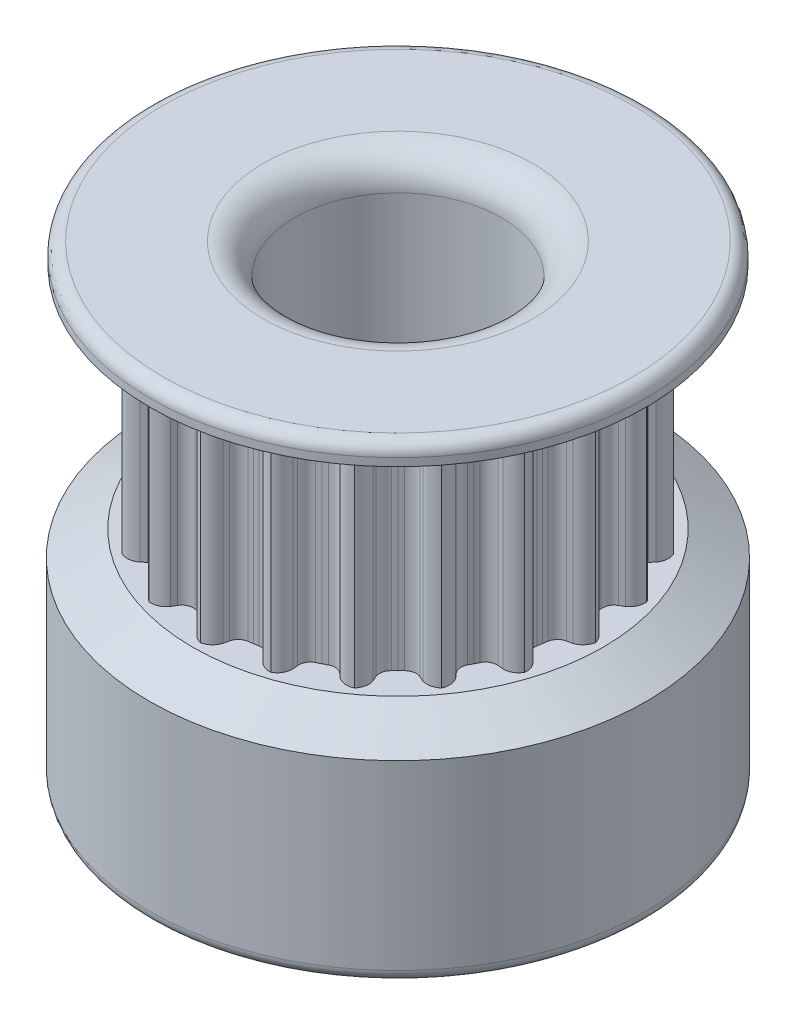
SolidWorks part; units mm, degrees
ref_plane "Plan de face" through (0, 0, 0) normal (0, 0, 1) x (1, 0, 0)
ref_plane "Plan de dessus" through (0, 0, 0) normal (0, 1, 0) x (1, 0, 0)
ref_plane "Plan de droite" through (0, 0, 0) normal (1, 0, 0) x (0, 0, -1)
sketch "Esquisse1" plane through (0, 0, 0) normal (0, 1, 0) x (1, 0, 0)
  circle A0 centre (0, 0) radius 7.935
  dimension "D1" = 15.87
extrude "Boss.-Extru.1" add sketch "Esquisse1" along normal blind 7
sketch "Esquisse2" plane through (0, 7, 0) normal (0, 1, 0) x (1, 0, 0)
  line L0 (0, 0) -> (0, 10.3573) construction
  line L1 (0, 0) -> (-1.2413, 7.8373) construction
  line L2 (0, 0) -> (1.2413, 7.8373) construction
  line L3 (-0.8681, 5.4812) -> (-0.7197, 5.5031)
  line L4 (-0.4122, 5.7909) -> (-0.3761, 5.9574)
  line L5 (0.4122, 5.7909) -> (0.3761, 5.9574)
  line L6 (0.8681, 5.4812) -> (0.7197, 5.5031)
  line L7 (2.5194, 4.9447) -> (2.3851, 5.0114)
  line L8 (1.3974, 5.6348) -> (1.4832, 5.7821)
  line L9 (0.8681, 5.4812) -> (1.016, 5.4562)
  line L10 (2.1815, 5.3801) -> (2.1987, 5.5496)
  line L11 (3.9241, 3.9241) -> (3.8169, 4.0291)
  line L12 (3.0703, 4.9272) -> (3.1974, 5.0407)
  line L13 (2.5194, 4.9447) -> (2.6524, 4.8752)
  line L14 (3.7373, 4.4426) -> (3.806, 4.5985)
  line L15 (4.9447, 2.5194) -> (4.8752, 2.6524)
  line L16 (4.4426, 3.7373) -> (4.5985, 3.806)
  line L17 (3.9241, 3.9241) -> (4.0291, 3.8169)
  line L18 (4.9272, 3.0703) -> (5.0407, 3.1974)
  line L19 (5.4812, 0.8681) -> (5.4562, 1.016)
  line L20 (5.3801, 2.1815) -> (5.5496, 2.1987)
  line L21 (4.9447, 2.5194) -> (5.0114, 2.3851)
  line L22 (5.6348, 1.3974) -> (5.7821, 1.4832)
  line L23 (5.4812, -0.8681) -> (5.5031, -0.7197)
  line L24 (5.7909, 0.4122) -> (5.9574, 0.3761)
  line L25 (5.4812, 0.8681) -> (5.5031, 0.7197)
  line L26 (5.7909, -0.4122) -> (5.9574, -0.3761)
  line L27 (4.9447, -2.5194) -> (5.0114, -2.3851)
  line L28 (5.6348, -1.3974) -> (5.7821, -1.4832)
  line L29 (5.4812, -0.8681) -> (5.4562, -1.016)
  line L30 (5.3801, -2.1815) -> (5.5496, -2.1987)
  line L31 (3.9241, -3.9241) -> (4.0291, -3.8169)
  line L32 (4.9272, -3.0703) -> (5.0407, -3.1974)
  line L33 (4.9447, -2.5194) -> (4.8752, -2.6524)
  line L34 (4.4426, -3.7373) -> (4.5985, -3.806)
  line L35 (2.5194, -4.9447) -> (2.6524, -4.8752)
  line L36 (3.7373, -4.4426) -> (3.806, -4.5985)
  line L37 (3.9241, -3.9241) -> (3.8169, -4.0291)
  line L38 (3.0703, -4.9272) -> (3.1974, -5.0407)
  line L39 (0.8681, -5.4812) -> (1.016, -5.4562)
  line L40 (2.1815, -5.3801) -> (2.1987, -5.5496)
  line L41 (2.5194, -4.9447) -> (2.3851, -5.0114)
  line L42 (1.3974, -5.6348) -> (1.4832, -5.7821)
  line L43 (-0.8681, -5.4812) -> (-0.7197, -5.5031)
  line L44 (0.4122, -5.7909) -> (0.3761, -5.9574)
  line L45 (0.8681, -5.4812) -> (0.7197, -5.5031)
  line L46 (-0.4122, -5.7909) -> (-0.3761, -5.9574)
  line L47 (-2.5194, -4.9447) -> (-2.3851, -5.0114)
  line L48 (-1.3974, -5.6348) -> (-1.4832, -5.7821)
  line L49 (-0.8681, -5.4812) -> (-1.016, -5.4562)
  line L50 (-2.1815, -5.3801) -> (-2.1987, -5.5496)
  line L51 (-3.9241, -3.9241) -> (-3.8169, -4.0291)
  line L52 (-3.0703, -4.9272) -> (-3.1974, -5.0407)
  line L53 (-2.5194, -4.9447) -> (-2.6524, -4.8752)
  line L54 (-3.7373, -4.4426) -> (-3.806, -4.5985)
  line L55 (-4.9447, -2.5194) -> (-4.8752, -2.6524)
  line L56 (-4.4426, -3.7373) -> (-4.5985, -3.806)
  line L57 (-3.9241, -3.9241) -> (-4.0291, -3.8169)
  line L58 (-4.9272, -3.0703) -> (-5.0407, -3.1974)
  line L59 (-5.4812, -0.8681) -> (-5.4562, -1.016)
  line L60 (-5.3801, -2.1815) -> (-5.5496, -2.1987)
  line L61 (-4.9447, -2.5194) -> (-5.0114, -2.3851)
  line L62 (-5.6348, -1.3974) -> (-5.7821, -1.4832)
  line L63 (-5.4812, 0.8681) -> (-5.5031, 0.7197)
  line L64 (-5.7909, -0.4122) -> (-5.9574, -0.3761)
  line L65 (-5.4812, -0.8681) -> (-5.5031, -0.7197)
  line L66 (-5.7909, 0.4122) -> (-5.9574, 0.3761)
  line L67 (-4.9447, 2.5194) -> (-5.0114, 2.3851)
  line L68 (-5.6348, 1.3974) -> (-5.7821, 1.4832)
  line L69 (-5.4812, 0.8681) -> (-5.4562, 1.016)
  line L70 (-5.3801, 2.1815) -> (-5.5496, 2.1987)
  line L71 (-3.9241, 3.9241) -> (-4.0291, 3.8169)
  line L72 (-4.9272, 3.0703) -> (-5.0407, 3.1974)
  line L73 (-4.9447, 2.5194) -> (-4.8752, 2.6524)
  line L74 (-4.4426, 3.7373) -> (-4.5985, 3.806)
  line L75 (-2.5194, 4.9447) -> (-2.6524, 4.8752)
  line L76 (-3.7373, 4.4426) -> (-3.806, 4.5985)
  line L77 (-3.9241, 3.9241) -> (-3.8169, 4.0291)
  line L78 (-3.0703, 4.9272) -> (-3.1974, 5.0407)
  line L79 (-0.8681, 5.4812) -> (-1.016, 5.4562)
  line L80 (-2.1815, 5.3801) -> (-2.1987, 5.5496)
  line L81 (-2.5194, 4.9447) -> (-2.3851, 5.0114)
  line L82 (-1.3974, 5.6348) -> (-1.4832, 5.7821)
  circle A0 centre (0, 0) radius 6.3 construction
  circle A1 centre (0, 0) radius 7.935 construction
  circle A2 centre (0, 0) radius 5.55 construction
  arc A3 (-0.7197, 5.5031) -> (-0.4122, 5.7909) centre (-0.7738, 5.8692) ccw
  arc A4 (-0.3761, 5.9574) -> (0, 6.3) centre (0.1018, 5.8105) cw
  arc A5 (0.3761, 5.9574) -> (0, 6.3) centre (-0.1018, 5.8105) ccw
  arc A6 (0.7197, 5.5031) -> (0.4122, 5.7909) centre (0.7738, 5.8692) cw
  arc A7 (2.3851, 5.0114) -> (2.1815, 5.3801) centre (2.5496, 5.3428) cw
  arc A8 (2.1987, 5.5496) -> (1.9468, 5.9917) centre (1.6987, 5.5575) ccw
  arc A9 (1.4832, 5.7821) -> (1.9468, 5.9917) centre (1.8923, 5.4946) cw
  arc A10 (1.016, 5.4562) -> (1.3974, 5.6348) centre (1.0777, 5.821) ccw
  arc A11 (3.8169, 4.0291) -> (3.7373, 4.4426) centre (4.0758, 4.2934) cw
  arc A12 (3.806, 4.5985) -> (3.703, 5.0968) centre (3.333, 4.7606) ccw
  arc A13 (3.1974, 5.0407) -> (3.703, 5.0968) centre (3.4976, 4.6409) cw
  arc A14 (2.6524, 4.8752) -> (3.0703, 4.9272) centre (2.8238, 5.2031) ccw
  arc A15 (4.8752, 2.6524) -> (4.9272, 3.0703) centre (5.2031, 2.8238) cw
  arc A16 (5.0407, 3.1974) -> (5.0968, 3.703) centre (4.6409, 3.4976) ccw
  arc A17 (4.5985, 3.806) -> (5.0968, 3.703) centre (4.7606, 3.333) cw
  arc A18 (4.0291, 3.8169) -> (4.4426, 3.7373) centre (4.2934, 4.0758) ccw
  arc A19 (5.4562, 1.016) -> (5.6348, 1.3974) centre (5.821, 1.0777) cw
  arc A20 (5.7821, 1.4832) -> (5.9917, 1.9468) centre (5.4946, 1.8923) ccw
  arc A21 (5.5496, 2.1987) -> (5.9917, 1.9468) centre (5.5575, 1.6987) cw
  arc A22 (5.0114, 2.3851) -> (5.3801, 2.1815) centre (5.3428, 2.5496) ccw
  arc A23 (5.5031, -0.7197) -> (5.7909, -0.4122) centre (5.8692, -0.7738) cw
  arc A24 (5.9574, -0.3761) -> (6.3, 0) centre (5.8105, 0.1018) ccw
  arc A25 (5.9574, 0.3761) -> (6.3, 0) centre (5.8105, -0.1018) cw
  arc A26 (5.5031, 0.7197) -> (5.7909, 0.4122) centre (5.8692, 0.7738) ccw
  arc A27 (5.0114, -2.3851) -> (5.3801, -2.1815) centre (5.3428, -2.5496) cw
  arc A28 (5.5496, -2.1987) -> (5.9917, -1.9468) centre (5.5575, -1.6987) ccw
  arc A29 (5.7821, -1.4832) -> (5.9917, -1.9468) centre (5.4946, -1.8923) cw
  arc A30 (5.4562, -1.016) -> (5.6348, -1.3974) centre (5.821, -1.0777) ccw
  arc A31 (4.0291, -3.8169) -> (4.4426, -3.7373) centre (4.2934, -4.0758) cw
  arc A32 (4.5985, -3.806) -> (5.0968, -3.703) centre (4.7606, -3.333) ccw
  arc A33 (5.0407, -3.1974) -> (5.0968, -3.703) centre (4.6409, -3.4976) cw
  arc A34 (4.8752, -2.6524) -> (4.9272, -3.0703) centre (5.2031, -2.8238) ccw
  arc A35 (2.6524, -4.8752) -> (3.0703, -4.9272) centre (2.8238, -5.2031) cw
  arc A36 (3.1974, -5.0407) -> (3.703, -5.0968) centre (3.4976, -4.6409) ccw
  arc A37 (3.806, -4.5985) -> (3.703, -5.0968) centre (3.333, -4.7606) cw
  arc A38 (3.8169, -4.0291) -> (3.7373, -4.4426) centre (4.0758, -4.2934) ccw
  arc A39 (1.016, -5.4562) -> (1.3974, -5.6348) centre (1.0777, -5.821) cw
  arc A40 (1.4832, -5.7821) -> (1.9468, -5.9917) centre (1.8923, -5.4946) ccw
  arc A41 (2.1987, -5.5496) -> (1.9468, -5.9917) centre (1.6987, -5.5575) cw
  arc A42 (2.3851, -5.0114) -> (2.1815, -5.3801) centre (2.5496, -5.3428) ccw
  arc A43 (-0.7197, -5.5031) -> (-0.4122, -5.7909) centre (-0.7738, -5.8692) cw
  arc A44 (-0.3761, -5.9574) -> (0, -6.3) centre (0.1018, -5.8105) ccw
  arc A45 (0.3761, -5.9574) -> (0, -6.3) centre (-0.1018, -5.8105) cw
  arc A46 (0.7197, -5.5031) -> (0.4122, -5.7909) centre (0.7738, -5.8692) ccw
  arc A47 (-2.3851, -5.0114) -> (-2.1815, -5.3801) centre (-2.5496, -5.3428) cw
  arc A48 (-2.1987, -5.5496) -> (-1.9468, -5.9917) centre (-1.6987, -5.5575) ccw
  arc A49 (-1.4832, -5.7821) -> (-1.9468, -5.9917) centre (-1.8923, -5.4946) cw
  arc A50 (-1.016, -5.4562) -> (-1.3974, -5.6348) centre (-1.0777, -5.821) ccw
  arc A51 (-3.8169, -4.0291) -> (-3.7373, -4.4426) centre (-4.0758, -4.2934) cw
  arc A52 (-3.806, -4.5985) -> (-3.703, -5.0968) centre (-3.333, -4.7606) ccw
  arc A53 (-3.1974, -5.0407) -> (-3.703, -5.0968) centre (-3.4976, -4.6409) cw
  arc A54 (-2.6524, -4.8752) -> (-3.0703, -4.9272) centre (-2.8238, -5.2031) ccw
  arc A55 (-4.8752, -2.6524) -> (-4.9272, -3.0703) centre (-5.2031, -2.8238) cw
  arc A56 (-5.0407, -3.1974) -> (-5.0968, -3.703) centre (-4.6409, -3.4976) ccw
  arc A57 (-4.5985, -3.806) -> (-5.0968, -3.703) centre (-4.7606, -3.333) cw
  arc A58 (-4.0291, -3.8169) -> (-4.4426, -3.7373) centre (-4.2934, -4.0758) ccw
  arc A59 (-5.4562, -1.016) -> (-5.6348, -1.3974) centre (-5.821, -1.0777) cw
  arc A60 (-5.7821, -1.4832) -> (-5.9917, -1.9468) centre (-5.4946, -1.8923) ccw
  arc A61 (-5.5496, -2.1987) -> (-5.9917, -1.9468) centre (-5.5575, -1.6987) cw
  arc A62 (-5.0114, -2.3851) -> (-5.3801, -2.1815) centre (-5.3428, -2.5496) ccw
  arc A63 (-5.5031, 0.7197) -> (-5.7909, 0.4122) centre (-5.8692, 0.7738) cw
  arc A64 (-5.9574, 0.3761) -> (-6.3, 0) centre (-5.8105, -0.1018) ccw
  arc A65 (-5.9574, -0.3761) -> (-6.3, 0) centre (-5.8105, 0.1018) cw
  arc A66 (-5.5031, -0.7197) -> (-5.7909, -0.4122) centre (-5.8692, -0.7738) ccw
  arc A67 (-5.0114, 2.3851) -> (-5.3801, 2.1815) centre (-5.3428, 2.5496) cw
  arc A68 (-5.5496, 2.1987) -> (-5.9917, 1.9468) centre (-5.5575, 1.6987) ccw
  arc A69 (-5.7821, 1.4832) -> (-5.9917, 1.9468) centre (-5.4946, 1.8923) cw
  arc A70 (-5.4562, 1.016) -> (-5.6348, 1.3974) centre (-5.821, 1.0777) ccw
  arc A71 (-4.0291, 3.8169) -> (-4.4426, 3.7373) centre (-4.2934, 4.0758) cw
  arc A72 (-4.5985, 3.806) -> (-5.0968, 3.703) centre (-4.7606, 3.333) ccw
  arc A73 (-5.0407, 3.1974) -> (-5.0968, 3.703) centre (-4.6409, 3.4976) cw
  arc A74 (-4.8752, 2.6524) -> (-4.9272, 3.0703) centre (-5.2031, 2.8238) ccw
  arc A75 (-2.6524, 4.8752) -> (-3.0703, 4.9272) centre (-2.8238, 5.2031) cw
  arc A76 (-3.1974, 5.0407) -> (-3.703, 5.0968) centre (-3.4976, 4.6409) ccw
  arc A77 (-3.806, 4.5985) -> (-3.703, 5.0968) centre (-3.333, 4.7606) cw
  arc A78 (-3.8169, 4.0291) -> (-3.7373, 4.4426) centre (-4.0758, 4.2934) ccw
  arc A79 (-1.016, 5.4562) -> (-1.3974, 5.6348) centre (-1.0777, 5.821) cw
  arc A80 (-1.4832, 5.7821) -> (-1.9468, 5.9917) centre (-1.8923, 5.4946) ccw
  arc A81 (-2.1987, 5.5496) -> (-1.9468, 5.9917) centre (-1.6987, 5.5575) cw
  arc A82 (-2.3851, 5.0114) -> (-2.1815, 5.3801) centre (-2.5496, 5.3428) ccw
  point P271 (0, 0)
  dimension "D2" = 12.6
  dimension "D3" = 0.75
  dimension "D5" = 0.5
  dimension "D6" = 0.37
  dimension "D1" = 9
  dimension "D4" = 0.15
  dimension "D7" = 20
extrude "Boss.-Extru.2" add sketch "Esquisse2" along normal blind 6.5
sketch "Esquisse3" plane through (0, 13.5, 0) normal (0, 1, 0) x (1, 0, 0)
  circle A0 centre (0, 0) radius 7.9
  dimension "D1" = 15.8
extrude "Boss.-Extru.3" add sketch "Esquisse3" along normal blind 1.45
sketch "Esquisse4" plane through (0, 14.95, 0) normal (0, 1, 0) x (1, 0, 0)
  circle A0 centre (0, 0) radius 3.3
  dimension "D1" = 6.6
extrude "Enlèv. mat.-Extru.1" cut sketch "Esquisse4" against normal up to next
ref_axis "Axe1" through (0, 0, 0) along (0, 1, 0)
sketch "Esquisse5" plane through (0, 0, 0) normal (0, 0, 1) x (1, 0, 0)
  line L0 (0, 0) -> (0, 14.95) construction
  line L1 (-7.935, 0) -> (7.935, 0) construction
  circle A0 centre (0, 3.75) radius 1.65
  dimension "D1" = 3.3
  dimension "D2" = 3.75
extrude "Enlèv. mat.-Extru.2" cut sketch "Esquisse5" against normal through all
fillet "Congé1" radius 1 2 edges at (0, 14.95, 3.3) (0, 0, 3.3)
fillet "Congé2" radius 0.4 1 edges at (0.3399, 2.1354, -7.9277)
fillet "Congé3" radius 0.4 2 edges at (0, 14.95, 7.9) (0, 0, 7.935)
chamfer "Chanfrein1" distance 0.8 angle 60 2 edges at (0, 7, 7.935) (0, 13.5, 7.9) first distance on face at (0, 0.4, 7.935) first distance on face at (0, 14.55, 7.9)
